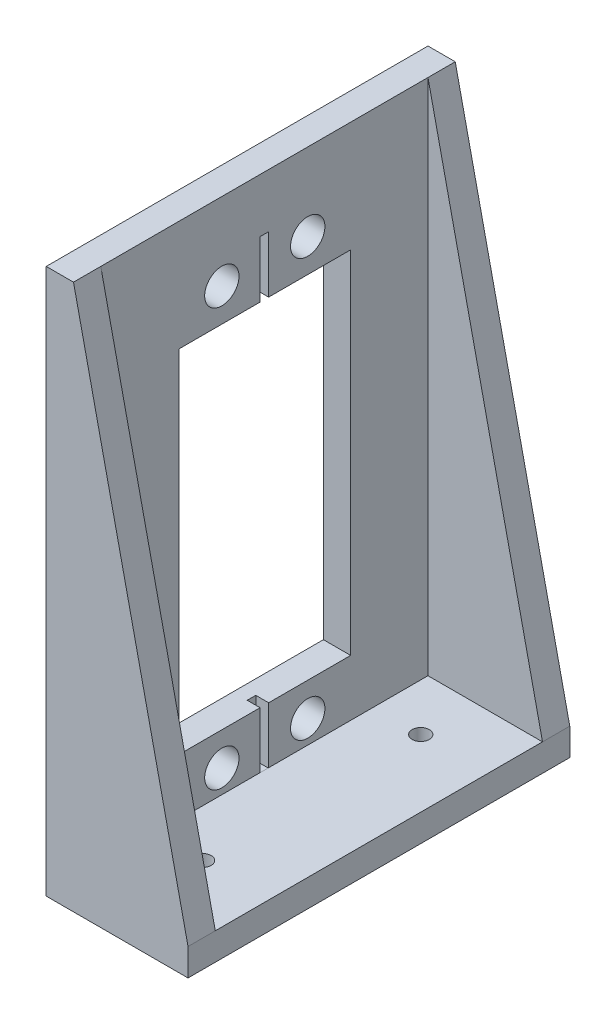
SolidWorks part; units mm, degrees
ref_plane "Front Plane" through (0, 0, 0) normal (0, 0, 1) x (1, 0, 0)
ref_plane "Top Plane" through (0, 0, 0) normal (0, 1, 0) x (1, 0, 0)
ref_plane "Right Plane" through (0, 0, 0) normal (1, 0, 0) x (0, 0, -1)
sketch "Sketch1" plane through (0, 0, 0) normal (0, 0, 1) x (1, 0, 0)
  line L0 (0, 0) -> (0, 63.5)
  line L1 (0, 63.5) -> (3.175, 63.5)
  line L2 (3.175, 63.5) -> (3.175, 3.175)
  line L3 (3.175, 3.175) -> (16.51, 3.175)
  line L4 (16.51, 3.175) -> (16.51, 0)
  line L5 (16.51, 0) -> (0, 0)
  dimension "D1" = 3.175
  dimension "D2" = 3.175
  dimension "D3" = 16.51
  dimension "D4" = 63.5
extrude "Boss-Extrude1" add sketch "Sketch1" along normal mid plane 44.45
sketch "Sketch3" plane through (0, 0, 22.225) normal (0, 0, 1) x (1, 0, 0)
  line L0 (3.175, 63.5) -> (16.51, 3.175)
  line L1 (16.51, 3.175) -> (3.175, 3.175)
  line L2 (3.175, 3.175) -> (3.175, 63.5)
extrude "Boss-Extrude2" add sketch "Sketch3" against normal blind 3.175
mirror "Mirror1" about plane through (0, 0, 0) normal (0, 0, 1) of "Boss-Extrude2"
sketch "Sketch4" plane through (0, 3.175, 0) normal (0, 1, 0) x (1, 0, 0)
  line L1 (3.175, 19.05) -> (16.51, 19.05) construction
  line L3 (3.175, 0) -> (16.51, 0) construction
  line L4 (3.175, -19.05) -> (3.175, 19.05) construction
  line L5 (16.51, -19.05) -> (16.51, 19.05) construction
  circle A0 centre (8.68, 12.7) radius 1
  circle A3 centre (8.68, -12.7) radius 1
  point P3 (0, 0)
  dimension "D1" = 2
  dimension "D2" = 6.35
  dimension "D3" = 5.505
extrude "Cut-Extrude2" cut sketch "Sketch4" against normal through all
sketch "Sketch5" plane through (3.175, 0, 0) normal (1, 0, 0) x (0, 0, -1)
  line L0 (-19.05, 63.5) -> (-19.05, 3.175) construction
  line L1 (-19.05, 3.175) -> (19.05, 3.175) construction
  circle A0 centre (-4.953, 5.875) radius 2
  circle A1 centre (5.047, 5.875) radius 2
  circle A2 centre (-4.953, 54.475) radius 2
  circle A3 centre (5.047, 54.475) radius 2
  point P16 (0, 0)
  point P17 (0, 0)
  dimension "D3" = 4
  dimension "D5" = 4
  dimension "D7" = 4
  dimension "D8" = 4
  dimension "D1" = 14.097
  dimension "D2" = 2.7
  dimension "D4" = 10
  dimension "D6" = 48.6
extrude "Cut-Extrude3" cut sketch "Sketch5" against normal through all
sketch "Sketch6" plane through (3.175, 0, 0) normal (1, 0, 0) x (0, 0, -1)
  line L0 (-9.953, 50.625) -> (10.047, 9.725) construction
  line L1 (-9.953, 50.625) -> (10.047, 50.625)
  line L2 (-9.953, 50.625) -> (-9.953, 9.725)
  line L3 (-9.953, 9.725) -> (10.047, 9.725)
  line L4 (10.047, 50.625) -> (10.047, 9.725)
  line L5 (10.047, 50.625) -> (-9.953, 9.725) construction
  line L6 (-4.953, 54.475) -> (5.047, 5.875) construction
  line L7 (-4.953, 5.875) -> (5.047, 54.475) construction
  point P12 (0.047, 30.175)
  point P13 (0.047, 30.175)
  dimension "D1" = 40.9
  dimension "D2" = 20
extrude "Cut-Extrude4" cut sketch "Sketch6" against normal through all
sketch "Sketch7" plane through (0, 50.625, 0) normal (0, -1, 0) x (1, 0, 0)
  line L0 (3.175, -10.047) -> (3.175, 9.953) construction
  line L1 (1.675, -0.5) -> (3.175, -0.5)
  line L2 (1.675, -0.5) -> (1.675, 0.5)
  line L3 (1.675, 0.5) -> (3.175, 0.5)
  line L4 (3.175, -0.5) -> (3.175, 0.5)
  line L5 (1.675, -0.5) -> (3.175, 0.5) construction
  line L6 (1.675, 0.5) -> (3.175, -0.5) construction
  line L7 (10.4775, 0) -> (-10.4775, 0) construction
  point P0 (2.425, 0)
  point P7 (0, 0)
  point P8 (0, 0)
  point P9 (2.425, 0)
  dimension "D1" = 1
  dimension "D2" = 1.5
extrude "Cut-Extrude5" cut sketch "Sketch7" against normal blind 6.604
extrude "Cut-Extrude6" cut sketch "Sketch7<2>" along normal blind 6.604 from surface starting at face at (1.5875, 9.725, -0.047)
sketch "Sketch7<2>" plane through (0, 50.625, 0) normal (0, -1, 0) x (1, 0, 0) same geometry as "Sketch7"
equation "\"D1@Sketch4\"=2mm"
equation "\"tightTol\" = 0.005in"
equation "\"normTol\"= 0.01in"
equation "\"looseTol\"= 0.02in"
equation "\"D2@Sketch5\"=2.7mm"
equation "\"D3@Sketch5\"=4mm"
equation "\"D4@Sketch5\"=10mm"
equation "\"D5@Sketch5\"=4mm"
equation "\"D6@Sketch5\"=48.6mm"
equation "\"D8@Sketch5\"=4mm"
equation "\"D1@Sketch6\"=40.9mm"
equation "\"D2@Sketch6\"=20mm"
equation "\"D1@Sketch7\"=1mm"
equation "\"D2@Sketch7\"=1.5mm"
equation "\"D7@Sketch5\"=4mm"
equation "\"D3@Sketch4\"=0.125000in+2.33mm"
